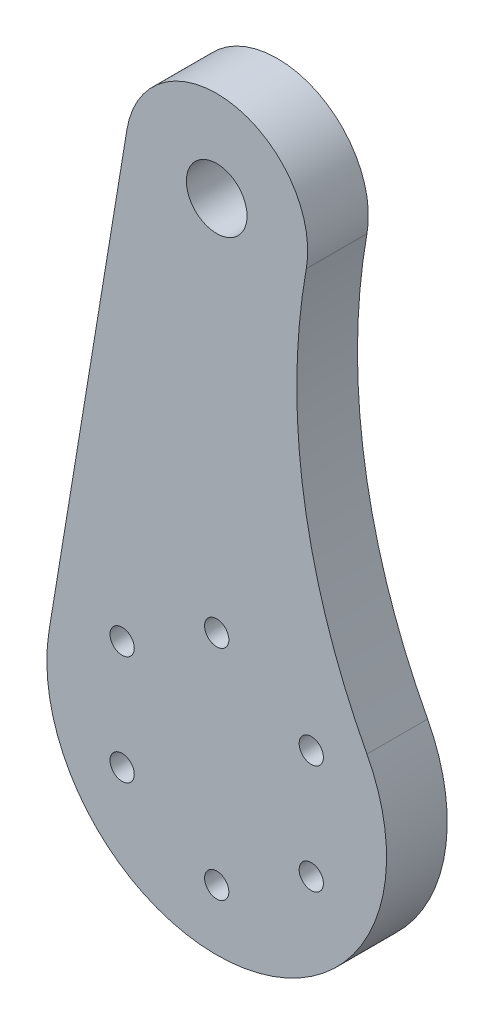
SolidWorks part; units mm, degrees
ref_plane "Front Plane" through (0, 0, 0) normal (1, 0, 0) x (0, 1, 0)
ref_plane "Top Plane" through (0, 0, 0) normal (0, 0, 1) x (0, 1, 0)
ref_plane "Right Plane" through (0, 0, 0) normal (0, 1, 0) x (-1, 0, 0)
sketch "Sketch1" plane through (0, 0, 0) normal (0, 0, 1) x (0, 1, 0)
  line L0 (4.55, 27.6278) -> (82.4375, 14.8006)
  circle A7 centre (0, 0) radius 18 construction
  arc A8 (4.55, 27.6278) -> (13.0689, -24.7629) centre (0, 0) ccw
  circle A9 centre (-18, 0) radius 2
  circle A10 centre (-9, 15.5885) radius 2
  circle A11 centre (9, 15.5885) radius 2
  circle A12 centre (18, 0) radius 2
  circle A13 centre (9, -15.5885) radius 2
  circle A14 centre (-9, -15.5885) radius 2
  arc A15 (13.0689, -24.7629) -> (77.3579, -14.7655) centre (59.7437, -113.202) cw
  arc A17 (82.4375, 14.8006) -> (77.3579, -14.7655) centre (80, 0) cw
  circle A18 centre (80, 0) radius 5
  point P18 (0, 0)
  dimension "D1" = 36
  dimension "D3" = 4
  dimension "D5" = 10
  dimension "D7" = 100
  dimension "D2" = 10
  dimension "D6" = 80
  dimension "D8" = 10
  dimension "D4" = 6
extrude "Boss-Extrude1" add sketch "Sketch1" along normal blind 10 contours A17 L0 A8 A15 A18 | A8 A14 A13 A12 A11 A10 A9 region at (-1.2753, 26.3194, 0)
equation "\"ThighLength\"= 150"
equation "\"BearingBore\"=10"
equation "\"MinShinWidth\"= 20"
equation "\"HipBore\"=27"
equation "\"ShinThickness\"=10"
equation "\"ThighThickness\"=10"
equation "\"MaxBending\"=135"
equation "\"MaxStretchingAngle\"= 50"
equation "\"ThighJointDistance\"=157.485"
equation "\"PivotDistance\"=30"
equation "\"ShinLength\"=120"
equation "\"BearingDiameter\"= 10"
equation "\"MotorDriverLength\"= 60mm"
equation "\"MotorLength\"= 60"
equation "\"MotorDriverWidth\"=44"
equation "\"MotorWidth\"= 37"
equation "\"InnerWallThickness\"=3"
equation "\"BatteryWidth\"= 60"
equation "\"OuterWallThickness\" = 6"
equation "\"CompartmentHeight\"=37"
equation "\"CompartmentWidth\"= \"MotorDriverLength\""
equation "\"MotorDiameter\"=37"
equation "\"BatteryHeight\"=24.2019"
equation "\"MotorDriverHeight\"=28"
equation "\"CircuitHeight\"=30"
equation "\"FanThickness\"= 10"
equation "\"FanHeight\"=50"
equation "\"MotorShaftHole\"=12"
equation "\"KneeLength\" =80"
equation "\"CircuitLength\"=50"
equation "\"ChessisInnerWidth\"= \"OuterWallThickness\" * 2 + \"MotorDriverLength\" + \"MotorDiameter\" + \"InnerWallThickness\" * 3 + \"CircuitLength\""
equation "\"ChessisHeight\"= \"BatteryHeight\" + 10 + \"InnerWallThickness\" + \"MotorDiameter\" + 10 + \"OuterWallThickness\" * 2"
equation "\"ChassisWidth\"= \"MotorDriverWidth\"*4+30"
equation "\"D6@Sketch1\"=\"KneeLength\""
equation "\"KneeRadius\"=100"
equation "\"D7@Sketch1\"=\"KneeRadius\""
